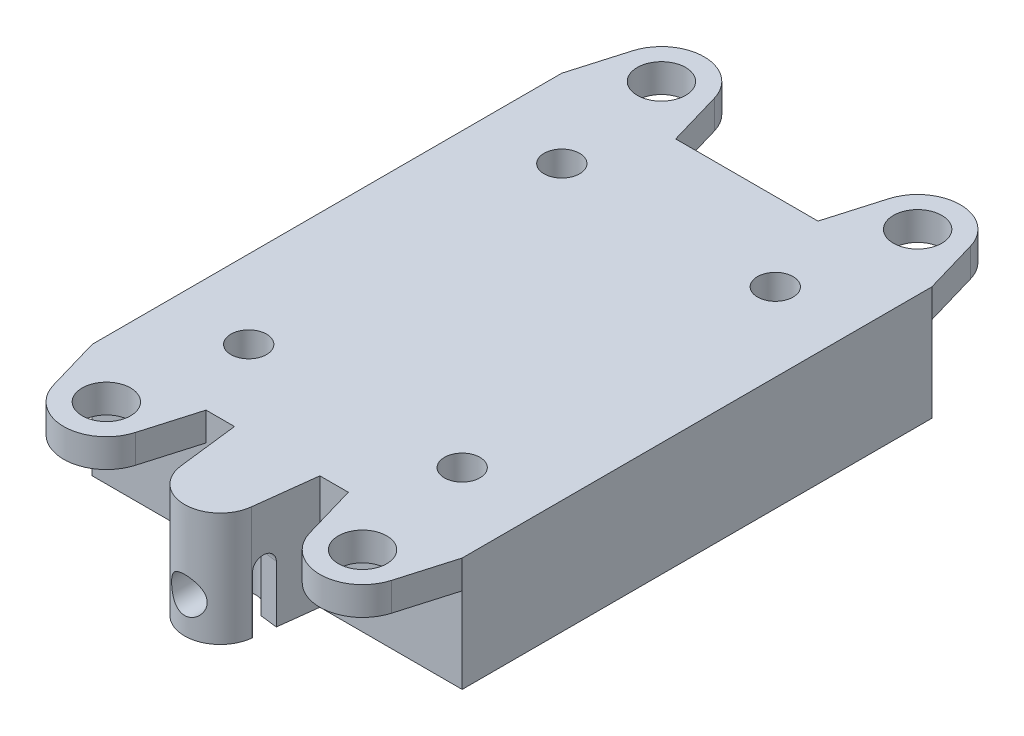
SolidWorks part; units mm, degrees
ref_plane "Front Plane" through (0, 0, 0) normal (0, 0, 1) x (1, 0, 0)
ref_plane "Top Plane" through (0, 0, 0) normal (0, 1, 0) x (1, 0, 0)
ref_plane "Right Plane" through (0, 0, 0) normal (1, 0, 0) x (0, 0, -1)
sketch "Sketch1" plane through (0, 0, 0) normal (0, 1, 0) x (1, 0, 0)
  line L0 (-2.4821, -4.299) -> (-3, 0)
  line L1 (-13, 33) -> (13, 33)
  line L2 (-13, 33) -> (-13, 0)
  line L3 (-13, 0) -> (-3, 0)
  line L4 (13, 33) -> (13, 0)
  line L5 (2.4821, -4.299) -> (3, 0)
  line L6 (3, 0) -> (13, 0)
  arc A0 (-2.4821, -4.299) -> (2.4821, -4.299) centre (0, -4) ccw
  dimension "D3" = 5
  dimension "D6" = 4
  dimension "D1" = 26
  dimension "D2" = 33
  dimension "D4" = 6
  dimension "D5" = 3
extrude "Boss-Extrude1" add sketch "Sketch1" along normal blind 8
sketch "Sketch2" plane through (0, 8, 0) normal (0, 1, 0) x (1, 0, 0)
  line L0 (-13, 16.5) -> (13, 16.5) construction
  line L1 (-13, 33) -> (-13, 0) construction
  line L2 (13, 0) -> (13, 33) construction
  line L3 (0, 33) -> (0, -9.541) construction
  line L4 (13, 33) -> (-13, 33) construction
  line L5 (-11.88, 36.84) -> (-13, 33)
  line L6 (-6.12, 36.84) -> (-5, 33)
  line L7 (-5, 33) -> (-13, 33)
  line L8 (5, 33) -> (13, 33)
  line L9 (6.12, 36.84) -> (5, 33)
  line L10 (11.88, 36.84) -> (13, 33)
  line L11 (-5, 0) -> (-13, 0)
  line L12 (-6.12, -3.84) -> (-5, 0)
  line L13 (-11.88, -3.84) -> (-13, 0)
  line L14 (11.88, -3.84) -> (13, 0)
  line L15 (6.12, -3.84) -> (5, 0)
  line L16 (5, 0) -> (13, 0)
  arc A0 (-6.12, 36.84) -> (-11.88, 36.84) centre (-9, 36) ccw
  arc A1 (6.12, 36.84) -> (11.88, 36.84) centre (9, 36) cw
  arc A2 (-6.12, -3.84) -> (-11.88, -3.84) centre (-9, -3) cw
  arc A3 (6.12, -3.84) -> (11.88, -3.84) centre (9, -3) ccw
  dimension "D1" = 6
  dimension "D2" = 3
  dimension "D3" = 4
extrude "Boss-Extrude2" add sketch "Sketch2" against normal blind 2
sketch "Sketch3" plane through (0, 0, 0) normal (0, -1, 0) x (1, 0, 0)
  line L0 (0, 0) -> (0, -4) construction
  line L1 (-11, -2) -> (11, -2)
  line L2 (-11, -2) -> (-11, -31)
  line L3 (-11, -31) -> (11, -31)
  line L4 (11, -2) -> (11, -31)
  line L5 (13, -16.5) -> (-13, -16.5) construction
  line L6 (13, 0) -> (13, -33) construction
  line L7 (-13, -33) -> (-13, 0) construction
  point P7 (0, -2)
  point P14 (-11, -16.5)
  dimension "D1" = 29
  dimension "D2" = 22
extrude "Cut-Extrude1" cut sketch "Sketch3" against normal blind 3
sketch "Sketch4" plane through (0, 0, 0) normal (0, -1, 0) x (-1, 0, 0)
  line L0 (0, 0) -> (0, -8.8942) construction
  circle A0 centre (0, -3) radius 1.5
  dimension "D1" = 3
  dimension "D2" = 3
extrude "Cut-Extrude2" cut sketch "Sketch4" against normal blind 5
hole_wizard "Tap Drill for M3x0.5 Tap1" positions "3DSketch1" profile "Sketch5" hole size "M3x0.5" standard "ANSI Metric" end condition up to next
sketch3d "3DSketch1"
  line L1 (0, 0, 6.5) -> (0, 9.9725, 6.5) construction
  line L3 (0, 0, 6.5) -> (-7.0757, 0, 6.5) construction
  arc A0 (-2.4821, 0, 4.299) -> (2.4821, 0, 4.299) centre (0, 0, 4) ccw construction
  point P0 (0, 2.5, 6.5)
  point P11 (0, 2.5, 4)
  dimension "D1" = 2.5
sketch "Sketch5" plane through (0, 2.5, 6.5) normal (1, 0, 0) x (0, -1, 0)
  line L0 (0, 0) -> (0, 2)
  line L1 (0, 2) -> (1.25, 2)
  line L2 (1.25, 2) -> (1.25, 0)
  line L5 (1.25, 0) -> (0, 0)
  line L11 (0, -6.35) -> (0, 107.95) construction
  dimension "Thru Hole Dia." = 2.5
  dimension "Thru Hole Depth" = 2
hole_wizard "M3 Clearance Hole1" positions "Sketch6" profile "Sketch7" hole size "M3" standard "ANSI Metric" end condition up to next
sketch "Sketch6" plane through (0, 6, 0) normal (0, -1, 0) x (-1, 0, 0)
  arc A0 (6.12, -3.84) -> (11.88, -3.84) centre (9, -3) ccw construction
  arc A1 (-11.88, -3.84) -> (-6.12, -3.84) centre (-9, -3) ccw construction
  arc A2 (11.88, 36.84) -> (6.12, 36.84) centre (9, 36) ccw construction
  arc A3 (-6.12, 36.84) -> (-11.88, 36.84) centre (-9, 36) ccw construction
  point P0 (9, -3)
  point P2 (-9, -3)
  point P4 (9, 36)
  point P6 (-9, 36)
sketch "Sketch7" plane through (-9, 6, 3) normal (1, 0, 0) x (0, 0, -1)
  line L0 (0, 0) -> (0, 2)
  line L1 (0, 2) -> (1.7, 2)
  line L2 (1.7, 2) -> (1.7, 0)
  line L5 (1.7, 0) -> (0, 0)
  line L11 (0, -6.35) -> (0, 107.95) construction
  dimension "Thru Hole Dia." = 3.4
  dimension "Thru Hole Depth" = 2
hole_wizard "Tap Drill for M3x0.5 Tap2" positions "Sketch8" profile "Sketch9" hole size "M3x0.5" standard "ANSI Metric" end condition up to next
sketch "Sketch8" plane through (0, 3, 0) normal (0, -1, 0) x (-1, 0, 0)
  line L0 (0, 2) -> (0, 31) construction
  line L1 (-11, 2) -> (11, 2) construction
  line L2 (11, 31) -> (-11, 31) construction
  line L4 (11, 16.5) -> (-11, 16.5) construction
  line L5 (11, 2) -> (11, 31) construction
  line L6 (-11, 31) -> (-11, 2) construction
  point P0 (7.5, 5.5)
  point P18 (7.5, 27.5)
  point P19 (-7.5, 27.5)
  point P20 (-7.5, 5.5)
  dimension "D1" = 7.5
  dimension "D2" = 11
sketch "Sketch9" plane through (-7.5, 3, -5.5) normal (1, 0, 0) x (0, 0, -1)
  line L0 (0, 0) -> (0, 5)
  line L1 (0, 5) -> (1.25, 5)
  line L2 (1.25, 5) -> (1.25, 0)
  line L5 (1.25, 0) -> (0, 0)
  line L11 (0, -6.35) -> (0, 107.95) construction
  dimension "Thru Hole Dia." = 2.5
  dimension "Thru Hole Depth" = 5
sketch "Sketch10" plane through (0, 3, 0) normal (0, -1, 0) x (-1, 0, 0)
  line L0 (-11, 16.5) -> (11, 16.5) construction
  line L1 (-5, 10) -> (-9, 10)
  line L2 (-5, 10) -> (-5, 23)
  line L3 (-5, 23) -> (-9, 23)
  line L4 (-9, 10) -> (-9, 23)
  line L5 (-11, 31) -> (-11, 2) construction
  line L6 (11, 2) -> (11, 31) construction
  line L7 (-7.5, 27.5) -> (-7.5, 5.5) construction
  point P10 (-9, 16.5)
  dimension "D1" = 13
  dimension "D2" = 4
  dimension "D3" = 2
extrude "Cut-Extrude3" cut sketch "Sketch10" against normal blind 2
sketch "Sketch19" plane through (2.9571, 0, 0.3563) normal (0.9928, 0, 0.1196) x (0.1196, 0, -0.9928)
  line L0 (-2.3912, 0) -> (-2.3912, 4)
  line L1 (-3.9713, 0) -> (0.3588, 0) construction
  line L2 (-3.9713, 8) -> (0.3588, 8) construction
  line L3 (0.3588, 8) -> (0.3588, 0) construction
  line L4 (-3.8912, 4) -> (-3.8912, 0)
  line L5 (-3.8912, 0) -> (-2.3912, 0)
  circle A0 centre (-3.1412, 4) radius 0.75 construction
  arc A1 (-2.3912, 4) -> (-3.8912, 4) centre (-3.1412, 4) ccw
  dimension "D1" = 1.5
  dimension "D2" = 4
  dimension "D3" = 3.5
extrude "Cut-Extrude4" cut sketch "Sketch19" against normal up to next
